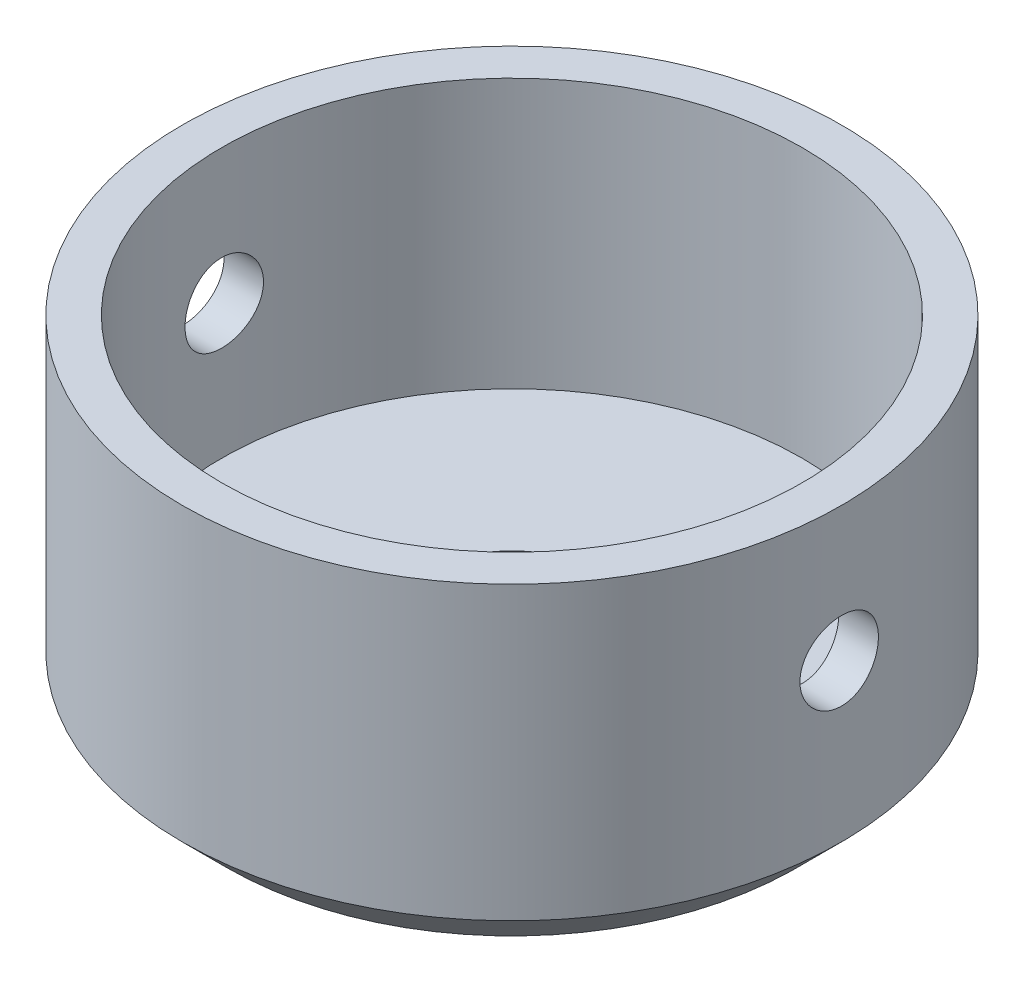
SolidWorks part; units mm, degrees
ref_plane "Front Plane" through (0, 0, 0) normal (0, 0, 1) x (1, 0, 0)
ref_plane "Top Plane" through (0, 0, 0) normal (0, 1, 0) x (1, 0, 0)
ref_plane "Right Plane" through (0, 0, 0) normal (1, 0, 0) x (0, 0, -1)
sketch "Sketch1" plane through (0, 0, 0) normal (0, 1, 0) x (1, 0, 0)
  circle A0 centre (0, 0) radius 12.7 construction
  circle A1 centre (0, 0) radius 14.7
  dimension "D1" = 25.4
  dimension "D2" = 2
extrude "Boss-Extrude1" add sketch "Sketch1" along normal blind 15
sketch "Sketch2" plane through (0, 15, 0) normal (0, 1, 0) x (1, 0, 0)
  circle A0 centre (0, 0) radius 12.95
  dimension "D1" = 25.9
extrude "Cut-Extrude1" cut sketch "Sketch2" against normal offset from surface (12 mm away) 3 up to face at (0, 0, 14.7)
sketch "Sketch3" plane through (0, 0, 0) normal (1, 0, 0) x (0, 0, -1)
  line L0 (0, 15) -> (0, 9) construction
  line L1 (12.95, 15) -> (-12.95, 15) construction
  circle A0 centre (0, 9) radius 1.75
  dimension "D2" = 3.5
  dimension "D1" = 6
extrude "Cut-Extrude2" cut sketch "Sketch3" against normal through all both and the other way through all
sketch "Sketch4" plane through (0, 0, 0) normal (0, -1, 0) x (1, 0, 0)
  circle A0 centre (0, 0) radius 4.1
  dimension "D1" = 8.2
extrude "Cut-Extrude3" cut sketch "Sketch4" against normal through all
chamfer "Chamfer1" distance 2 angle 45 1 edges at (0, 0, 14.7)
